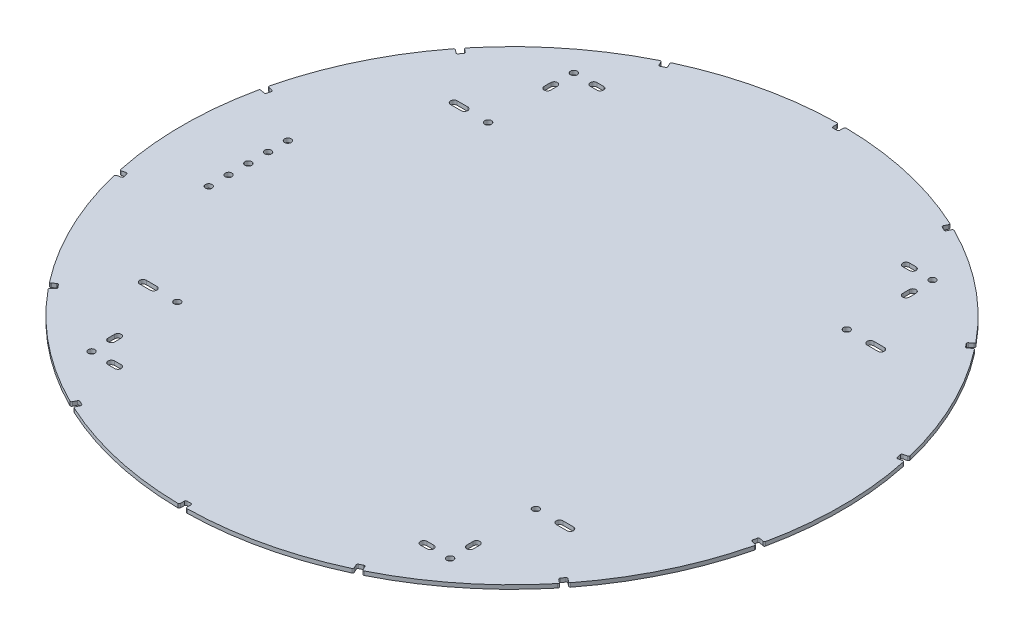
SolidWorks part; units mm, degrees
ref_plane "Front Plane" through (0, 0, 0) normal (0, 0, 1) x (1, 0, 0)
ref_plane "Top Plane" through (0, 0, 0) normal (0, 1, 0) x (1, 0, 0)
ref_plane "Right Plane" through (0, 0, 0) normal (1, 0, 0) x (0, 0, -1)
sketch "Sketch1" plane through (0, 0, 0) normal (0, 1, 0) x (1, 0, 0)
  circle A0 centre (0, 0) radius 250
extrude "Boss-Extrude1" add sketch "Sketch1" along normal blind 3
sketch "Sketch11" plane through (0, 3, 0) normal (0, 1, 0) x (1, 0, 0)
  line L1 (1.5, 245) -> (-1.5, 245)
  line L2 (2.5, 246) -> (2.5, 255)
  line L3 (2.5, 255) -> (-2.5, 255)
  line L4 (-2.5, 246) -> (-2.5, 255)
  line L5 (2.5, 245) -> (-2.5, 255) construction
  line L6 (2.5, 255) -> (-2.5, 245) construction
  circle A0 centre (0, 0) radius 250 construction
  arc A1 (2.5, 246) -> (1.5, 245) centre (1.5, 246) cw
  arc A2 (-1.5, 245) -> (-2.5, 246) centre (-1.5, 246) cw
  point P0 (0, 250)
  dimension "D3" = 1
  dimension "D1" = 10
  dimension "D2" = 5
extrude "Cut-Extrude5" cut sketch "Sketch11" against normal blind 4
fillet "Fillet1" radius 1 2 edges at (2.5, 1.5, -249.9875) (-2.5, 1.5, -249.9875)
pattern_circular "CirPattern1" count 14 over 360 about axis through (0, 3, 0) along (0, -1, 0) of "Cut-Extrude5", "Fillet1"
sketch "Sketch20" plane through (0, 0, 0) normal (0, -1, 0) x (1, 0, 0)
  line L0 (-166.5, -117.9) -> (-148.647, -117.9) construction
  line L1 (-162, -117.9) -> (-154, -117.9) construction
  line L2 (-162, -115.4) -> (-154, -115.4)
  line L3 (-162, -120.4) -> (-154, -120.4)
  line L4 (0, -1.65) -> (0, 1.65) construction
  line L5 (166.5, -117.9) -> (148.647, -117.9) construction
  line L6 (162, -117.9) -> (154, -117.9) construction
  line L7 (162, -115.4) -> (154, -115.4)
  line L8 (162, -120.4) -> (154, -120.4)
  line L9 (1.65, 0) -> (-1.65, 0) construction
  line L10 (162, 117.9) -> (154, 117.9) construction
  line L11 (162, 115.4) -> (154, 115.4)
  line L12 (162, 120.4) -> (154, 120.4)
  line L13 (-162, 117.9) -> (-154, 117.9) construction
  line L14 (-162, 115.4) -> (-154, 115.4)
  line L15 (-162, 120.4) -> (-154, 120.4)
  line L16 (-166.5, 117.9) -> (-148.647, 117.9) construction
  line L17 (166.5, 117.9) -> (148.647, 117.9) construction
  arc A0 (-164, -115.4) -> (-164, -120.4) centre (-164, -117.9) ccw construction
  arc A1 (-162, -115.4) -> (-162, -120.4) centre (-162, -117.9) ccw
  arc A2 (-154, -120.4) -> (-154, -115.4) centre (-154, -117.9) ccw
  arc A3 (162, -115.4) -> (162, -120.4) centre (162, -117.9) cw
  arc A4 (154, -120.4) -> (154, -115.4) centre (154, -117.9) cw
  arc A5 (162, 115.4) -> (162, 120.4) centre (162, 117.9) ccw
  arc A6 (154, 120.4) -> (154, 115.4) centre (154, 117.9) ccw
  arc A7 (-162, 115.4) -> (-162, 120.4) centre (-162, 117.9) cw
  arc A8 (-154, 120.4) -> (-154, 115.4) centre (-154, 117.9) cw
  point P8 (-158, -117.9)
  point P20 (158, -117.9)
  point P29 (158, 117.9)
  point P36 (-158, 117.9)
  dimension "D1" = 2.5
  dimension "D2" = 8
  dimension "D3" = 158
extrude "Cut-Extrude14" cut sketch "Sketch20" against normal blind 14
sketch "Sketch22" plane through (0, 3, 0) normal (0, 1, 0) x (1, 0, 0)
  line L0 (-1.65, 0) -> (1.65, 0) construction
  line L1 (0, -1.65) -> (0, 1.65) construction
  circle A0 centre (-136, -117.9) radius 2.5
  circle A1 centre (-136, 117.9) radius 2.5
  circle A2 centre (136, 117.9) radius 2.5
  circle A3 centre (136, -117.9) radius 2.5
  circle A4 centre (-136, 182.9) radius 2.5
  circle A5 centre (136, 182.9) radius 2.5
  circle A6 centre (-136, -182.9) radius 2.5
  circle A7 centre (136, -182.9) radius 2.5
  dimension "D1" = 2
extrude "Cut-Extrude16" cut sketch "Sketch22" against normal blind 14
sketch "Sketch26" plane through (0, 3, 0) normal (0, 1, 0) x (1, 0, 0)
  line L0 (-136, 162.9) -> (-136, 167.9) construction
  line L1 (-138.5, 162.9) -> (-138.5, 167.9)
  line L2 (-133.5, 162.9) -> (-133.5, 167.9)
  line L3 (-116, 182.9) -> (-121, 182.9) construction
  line L4 (-116, 180.4) -> (-121, 180.4)
  line L5 (-116, 185.4) -> (-121, 185.4)
  line L6 (0, -1.65) -> (0, 1.65) construction
  line L7 (116, 182.9) -> (121, 182.9) construction
  line L8 (116, 180.4) -> (121, 180.4)
  line L9 (116, 185.4) -> (121, 185.4)
  line L10 (136, 162.9) -> (136, 167.9) construction
  line L11 (138.5, 162.9) -> (138.5, 167.9)
  line L12 (133.5, 162.9) -> (133.5, 167.9)
  line L13 (-1.65, 0) -> (1.65, 0) construction
  line L14 (116, -182.9) -> (121, -182.9) construction
  line L15 (116, -180.4) -> (121, -180.4)
  line L16 (116, -185.4) -> (121, -185.4)
  line L17 (136, -162.9) -> (136, -167.9) construction
  line L18 (138.5, -162.9) -> (138.5, -167.9)
  line L19 (133.5, -162.9) -> (133.5, -167.9)
  line L20 (-136, -162.9) -> (-136, -167.9) construction
  line L21 (-138.5, -162.9) -> (-138.5, -167.9)
  line L22 (-133.5, -162.9) -> (-133.5, -167.9)
  line L23 (-116, -182.9) -> (-121, -182.9) construction
  line L24 (-116, -180.4) -> (-121, -180.4)
  line L25 (-116, -185.4) -> (-121, -185.4)
  arc A0 (-138.5, 162.9) -> (-133.5, 162.9) centre (-136, 162.9) ccw
  arc A1 (-133.5, 167.9) -> (-138.5, 167.9) centre (-136, 167.9) ccw
  circle A2 centre (-136, 182.9) radius 2.5 construction
  arc A3 (-116, 180.4) -> (-116, 185.4) centre (-116, 182.9) ccw
  arc A4 (-121, 185.4) -> (-121, 180.4) centre (-121, 182.9) ccw
  arc A5 (116, 180.4) -> (116, 185.4) centre (116, 182.9) cw
  arc A6 (121, 185.4) -> (121, 180.4) centre (121, 182.9) cw
  arc A7 (138.5, 162.9) -> (133.5, 162.9) centre (136, 162.9) cw
  arc A8 (133.5, 167.9) -> (138.5, 167.9) centre (136, 167.9) cw
  arc A9 (116, -180.4) -> (116, -185.4) centre (116, -182.9) ccw
  arc A10 (121, -185.4) -> (121, -180.4) centre (121, -182.9) ccw
  arc A11 (138.5, -162.9) -> (133.5, -162.9) centre (136, -162.9) ccw
  arc A12 (133.5, -167.9) -> (138.5, -167.9) centre (136, -167.9) ccw
  arc A13 (-138.5, -162.9) -> (-133.5, -162.9) centre (-136, -162.9) cw
  arc A14 (-133.5, -167.9) -> (-138.5, -167.9) centre (-136, -167.9) cw
  arc A15 (-116, -180.4) -> (-116, -185.4) centre (-116, -182.9) cw
  arc A16 (-121, -185.4) -> (-121, -180.4) centre (-121, -182.9) cw
  point P3 (-136, 165.4)
  point P12 (-118.5, 182.9)
  point P21 (118.5, 182.9)
  point P28 (136, 165.4)
  point P37 (118.5, -182.9)
  point P44 (136, -165.4)
  point P51 (-136, -165.4)
  point P58 (-118.5, -182.9)
  dimension "D1" = 2.5
  dimension "D4" = 2.5
  dimension "D2" = 5
  dimension "D3" = 17.5
  dimension "D5" = 5
  dimension "D6" = 17.5
extrude "Cut-Extrude19" cut sketch "Sketch26" against normal blind 4
sketch "Sketch28" plane through (0, 3, 0) normal (0, 1, 0) x (1, 0, 0)
  line L0 (-1.65, 0) -> (1.65, 0) construction
  circle A0 centre (-200, 0) radius 2.5
  circle A1 centre (-200, -15) radius 2.5
  circle A2 centre (-200, -30) radius 2.5
  circle A3 centre (-200, 30) radius 2.5
  circle A4 centre (-200, 15) radius 2.5
  dimension "D1" = 200
  dimension "D2" = 3
extrude "Cut-Extrude20" cut sketch "Sketch28" against normal blind 10
